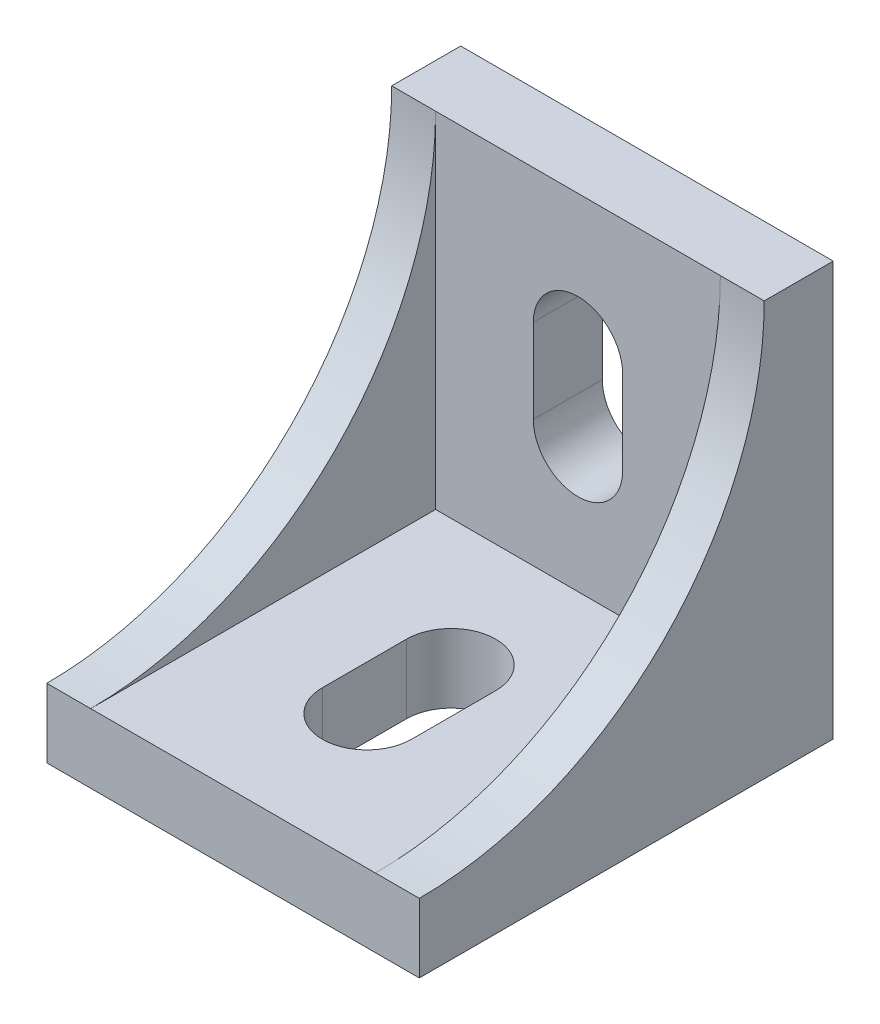
SolidWorks part; units mm, degrees
ref_plane "Front Plane" through (0, 0, 0) normal (0, 0, 1) x (1, 0, 0)
ref_plane "Top Plane" through (0, 0, 0) normal (0, 1, 0) x (1, 0, 0)
ref_plane "Right Plane" through (0, 0, 0) normal (1, 0, 0) x (0, 0, -1)
sketch "Sketch1" plane through (0, 0, 0) normal (0, 1, 0) x (1, 0, 0)
  line L1 (-13.5, -15) -> (13.5, -15)
  line L2 (-13.5, -15) -> (-13.5, 15)
  line L3 (-13.5, 15) -> (13.5, 15)
  line L4 (13.5, -15) -> (13.5, 15)
  line L5 (0, 15) -> (0, -15) construction
  line L6 (-13.5, 0) -> (13.5, 0) construction
  point P0 (0, 0)
  dimension "D1" = 27
  dimension "D2" = 30
extrude "Boss-Extrude1" add sketch "Sketch1" along normal blind 30
sketch "Sketch2" plane through (0, 30, 0) normal (0, 1, 0) x (1, 0, 0)
  line L0 (-13.5, -15) -> (13.5, -15) construction
  line L1 (-10.32, 10) -> (10.32, 10)
  line L2 (-10.32, 10) -> (-10.32, -15)
  line L3 (-10.32, -15) -> (10.32, -15)
  line L4 (10.32, 10) -> (10.32, -15)
  line L5 (0, -15) -> (0, 10) construction
  line L6 (-10.32, -2.5) -> (10.32, -2.5) construction
  line L7 (13.5, 15) -> (-13.5, 15) construction
  point P0 (0, -2.5)
  dimension "D1" = 20.64
  dimension "D2" = 5
extrude "Cut-Extrude1" cut sketch "Sketch2" against normal offset from surface (25 mm away) 5 up to face at (0, 0, 0)
sketch "Sketch3" plane through (0, 0, 0) normal (1, 0, 0) x (0, 0, -1)
  line L0 (-15, 30) -> (-15, 0) construction
  line L1 (10, 30) -> (-15, 30)
  line L2 (-15, 30) -> (-15, 5)
  arc A0 (10, 30) -> (-15, 5) centre (-15, 30) cw
extrude "Cut-Extrude2" cut sketch "Sketch3" against normal through all both and the other way through all
sketch "Sketch4" plane through (0, 5, 0) normal (0, 1, 0) x (1, 0, 0)
  line L0 (0, 0.805) -> (0, -5.295) construction
  line L1 (3.235, 0.805) -> (3.235, -5.295)
  line L2 (-3.235, 0.805) -> (-3.235, -5.295)
  line L3 (-10.32, -15) -> (10.32, -15) construction
  arc A0 (3.235, 0.805) -> (-3.235, 0.805) centre (0, 0.805) ccw
  arc A1 (-3.235, -5.295) -> (3.235, -5.295) centre (0, -5.295) ccw
  point P3 (0, -2.245)
  dimension "D3" = 9.705
  dimension "D1" = 6.47
  dimension "D2" = 6.1
sketch "Sketch5" plane through (0, 0, 0) normal (1, 0, 0) x (0, 0, -1)
  line L0 (10, 5) -> (10, 30) construction
  line L1 (-2.245, 5) -> (-2.245, -1.5201)
  line L3 (10, 17.245) -> (15, 17.245)
  line L4 (15, 30) -> (15, 0) construction
  arc A0 (-2.245, 5) -> (10, 17.245) centre (10, 5) cw
sweep "Cut-Sweep1" cut profiles "Sketch4" path "Sketch5"
extrude "Cut-Extrude3" cut sketch "Sketch4<2>" against normal through all
sketch "Sketch4<2>" plane through (0, 5, 0) normal (0, 1, 0) x (1, 0, 0) same geometry as "Sketch4"
sketch "Sketch12" plane through (0, 0, 0) normal (0, -1, 0) x (1, 0, 0)
  line L0 (0, -15) -> (0, 15) construction
  line L1 (13.5, -15) -> (-13.5, -15) construction
  line L2 (-13.5, 15) -> (13.5, 15) construction
  line L4 (-3, 11.9) -> (3, 11.9)
  line L5 (-3, 11.9) -> (-3, 9.8)
  line L6 (-3, 9.8) -> (3, 9.8)
  line L7 (3, 11.9) -> (3, 9.8)
  line L8 (0, 9.8) -> (0, 11.9) construction
  line L9 (-3, 10.85) -> (3, 10.85) construction
  point P6 (0, 10.85)
  dimension "D1" = 6
  dimension "D2" = 2.1
  dimension "D3" = 3.1
extrude "Boss-Extrude2" add sketch "Sketch12" along normal mid plane 3.3
pattern_linear "LPattern1" count 2 spacing 21.42 along (0, 0, -1) of "Boss-Extrude2"
pattern_circular "CirPattern1" count 2 every 90 about axis through (-13.5, 0, -15) along (-1, 0, 0) of "Boss-Extrude2", "LPattern1"
